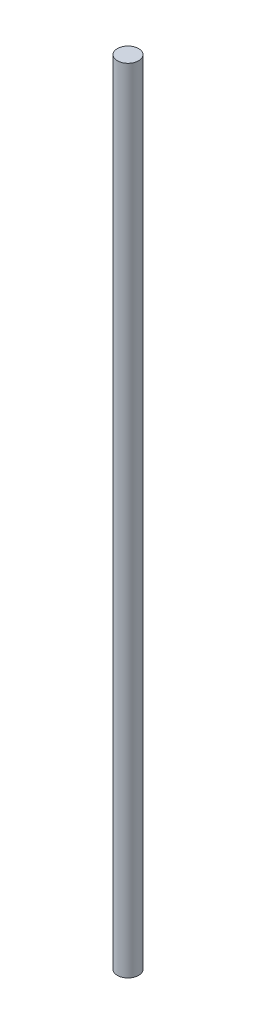
SolidWorks part; units mm, degrees
ref_plane "Front Plane" through (0, 0, 0) normal (0, 0, 1) x (1, 0, 0)
ref_plane "Top Plane" through (0, 0, 0) normal (0, 1, 0) x (1, 0, 0)
ref_plane "Right Plane" through (0, 0, 0) normal (1, 0, 0) x (0, 0, -1)
sketch "Skizze2" plane through (0, 0, 0) normal (0, 1, 0) x (1, 0, 0)
  circle A0 centre (0, 0) radius 6
extrude "Aufsatz-Linear austragen1" add sketch "Skizze2" along normal blind 224 and the other way blind 224
